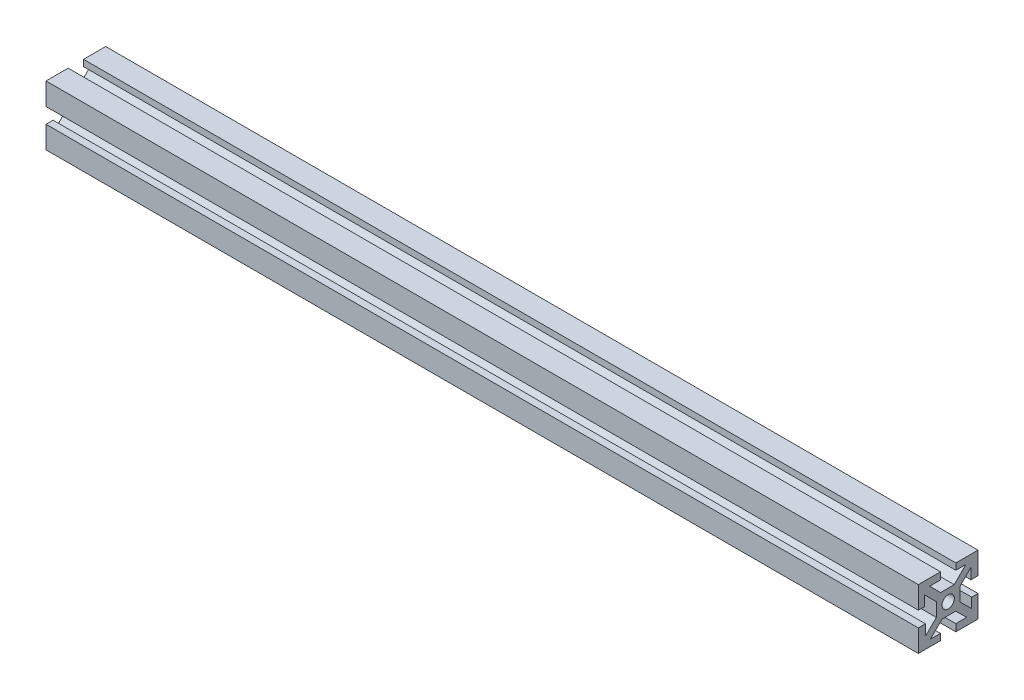
SolidWorks part; units mm, degrees
ref_plane "Front Plane" through (0, 0, 0) normal (0, 0, 1) x (1, 0, 0)
ref_plane "Top Plane" through (0, 0, 0) normal (0, 1, 0) x (1, 0, 0)
ref_plane "Right Plane" through (0, 0, 0) normal (1, 0, 0) x (0, 0, -1)
sketch "Sketch1" plane through (0, 0, 0) normal (1, 0, 0) x (0, 0, -1)
  line L0 (2.5534, 5) -> (7.4749, 9.9215)
  line L1 (-5, 5) -> (5, 5)
  line L2 (-5, 5) -> (-5, -5)
  line L3 (-5, -5) -> (5, -5)
  line L4 (5, 5) -> (5, -5)
  line L5 (-5, 5) -> (5, -5) construction
  line L6 (-5, -5) -> (5, 5) construction
  line L7 (7.4749, 9.9215) -> (9.5962, 7.8001)
  line L8 (9.5962, 7.8001) -> (5, 3.2039)
  line L9 (5, 5) -> (13.6489, 13.6489) construction
  line L10 (7.4749, 9.9215) -> (3.24, 9.9215)
  line L11 (3.24, 9.9215) -> (3.24, 12.5962)
  line L12 (3.24, 12.5962) -> (12.5962, 12.5962)
  line L13 (9.5962, 7.8001) -> (9.5962, 3.24)
  line L14 (9.5962, 3.24) -> (12.5962, 3.24)
  line L15 (12.5962, 3.24) -> (12.5962, 12.5962)
  line L17 (0, 0) -> (0, 24.089) construction
  line L18 (0, 0) -> (23.75, 0) construction
  circle A0 centre (0, 0) radius 2.605
  point P0 (0, 0)
  dimension "D1" = 5.21
  dimension "D2" = 10
  dimension "D3" = 10
  dimension "D4" = 3
  dimension "D5" = 1.27
  dimension "D6" = 6.5
  dimension "D7" = 3.24
  dimension "D8" = 3.24
  dimension "D9" = 3
extrude "Boss-Extrude1" add sketch "Sketch1" along normal blind 368.3 contours L4 L1 L2 L3 A0 | L8 L7 L0 L1 L4 | L14 L15 L12 L11 L10 L7 L13 region at (0, 4.8586, -3.7767) region at (0, 6.7479, -6.3823) region at (0, 9.18, -9.3105)
ref_axis "Axis1" through (0, 0, 0) along (1, 0, 0)
pattern_circular "CirPattern1" count 4 over 360 about axis through (0, 0, 0) along (1, 0, 0) of "Boss-Extrude1"
